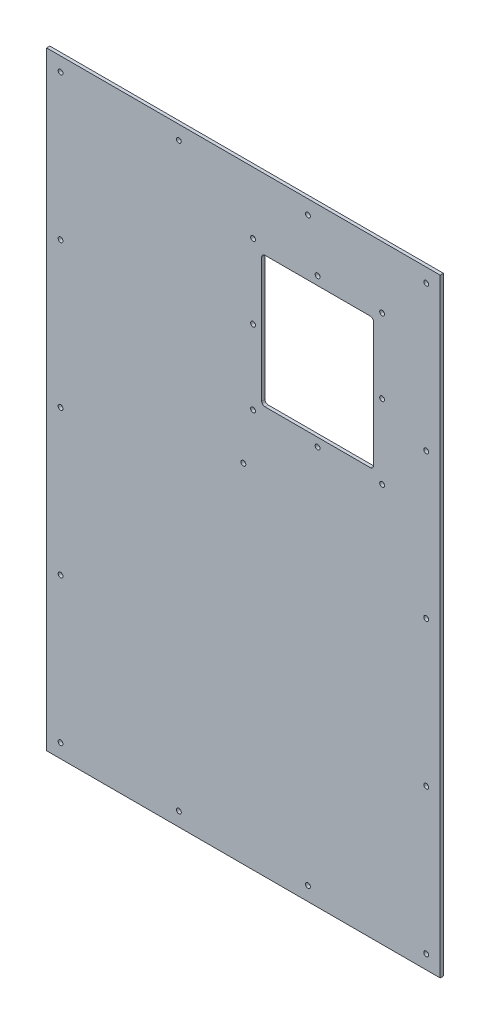
SolidWorks part; units mm, degrees
ref_plane "Спереди" through (0, 0, 0) normal (0, 0, 1) x (1, 0, 0)
ref_plane "Сверху" through (0, 0, 0) normal (0, 1, 0) x (1, 0, 0)
ref_plane "Справа" through (0, 0, 0) normal (1, 0, 0) x (0, 0, -1)
sketch "Эскиз1" plane through (0, 0, 0) normal (0, 0, 1) x (1, 0, 0)
  line L0 (0, 0) -> (366, 0)
  line L1 (0, 0) -> (0, 566)
  line L2 (366, 0) -> (366, 566)
  line L3 (0, 566) -> (366, 566)
  dimension "D1" = 566
  dimension "D2" = 366
extrude "Бобышка-Вытянуть1" add sketch "Эскиз1" along normal blind 3
sketch "Эскиз2" plane through (0, 0, 3) normal (0, 0, 1) x (1, 0, 0)
  line L0 (3, 563) -> (363, 563) construction
  line L1 (3, 563) -> (3, 3) construction
  line L2 (363, 563) -> (363, 3) construction
  line L3 (3, 3) -> (363, 3) construction
  line L4 (0, 566) -> (0, 0) construction
  line L5 (0, 0) -> (366, 0) construction
  dimension "D1" = 560
  dimension "D2" = 360
  dimension "D3" = 3
  dimension "D4" = 3
sketch "Эскиз5" plane through (0, 0, 0) normal (0, 0, -1) x (-1, 0, 0)
  line L0 (-353, 553) -> (-13, 553) construction
  line L1 (-353, 553) -> (-353, 13) construction
  line L2 (-13, 553) -> (-13, 13) construction
  line L3 (-353, 13) -> (-13, 13) construction
  line L4 (-366, 566) -> (0, 566) construction
  line L5 (-366, 0) -> (-366, 566) construction
  line L6 (0, 566) -> (0, 0) construction
  line L7 (0, 0) -> (-366, 0) construction
  line L8 (-366, 23) -> (-343, 23) construction
  line L9 (-366, 23) -> (-366, 0) construction
  line L10 (-343, 23) -> (-343, 0) construction
  line L11 (-366, 0) -> (-343, 0) construction
  line L12 (0, 0) -> (0, 23) construction
  line L13 (0, 0) -> (-23, 0) construction
  line L14 (0, 23) -> (-23, 23) construction
  line L15 (-23, 0) -> (-23, 23) construction
  line L16 (-366, 566) -> (-343, 566) construction
  line L17 (-366, 566) -> (-366, 543) construction
  line L18 (-343, 566) -> (-343, 543) construction
  line L19 (-366, 543) -> (-343, 543) construction
  line L20 (0, 566) -> (0, 543) construction
  line L21 (0, 566) -> (-23, 566) construction
  line L22 (0, 543) -> (-23, 543) construction
  line L23 (-23, 566) -> (-23, 543) construction
  line L24 (-13, 283) -> (-353, 283) construction
  line L25 (-183, 553) -> (-183, 13) construction
  circle A0 centre (-353, 553) radius 2.25
  circle A1 centre (-13, 553) radius 2.25
  circle A3 centre (-243, 553) radius 2.25
  circle A4 centre (-123, 553) radius 2.25
  circle A5 centre (-353, 418) radius 2.25
  circle A6 centre (-353, 283) radius 2.25
  circle A7 centre (-353, 148) radius 2.25
  circle A8 centre (-353, 13) radius 2.25
  circle A11 centre (-13, 418) radius 2.25
  circle A12 centre (-13, 283) radius 2.25
  circle A13 centre (-13, 148) radius 2.25
  circle A14 centre (-13, 13) radius 2.25
  circle A18 centre (-123, 13) radius 2.25
  circle A19 centre (-243, 13) radius 2.25
  dimension "D13" = 4.5
  dimension "D14" = 4.5
  dimension "D15" = 110
  dimension "D17" = 4.5
  dimension "D18" = 4.5
  dimension "D19" = 110
  dimension "D22" = 135
  dimension "D23" = 135
  dimension "D24" = 110
  dimension "D25" = 5
  dimension "D26" = 135
  dimension "D27" = 110
  dimension "D29" = 4.5
  dimension "D31" = 4.5
  dimension "D1" = 13
  dimension "D2" = 13
  dimension "D3" = 13
  dimension "D4" = 13
  dimension "D5" = 23
  dimension "D6" = 23
  dimension "D7" = 23
  dimension "D8" = 23
  dimension "D9" = 23
  dimension "D10" = 23
  dimension "D11" = 23
  dimension "D12" = 23
  dimension "D21" = 5
extrude "Вырез-Вытянуть2" cut sketch "Эскиз5" against normal through all
sketch "Эскиз6" plane through (0, 0, 3) normal (0, 0, 1) x (1, 0, 0)
  line L0 (200, 378.5) -> (200, 500.5) construction
  line L1 (200, 378.5) -> (200, 500.5)
  line L2 (200, 500.5) -> (304, 500.5) construction
  line L3 (200, 500.5) -> (304, 500.5)
  line L4 (304, 500.5) -> (304, 378.5) construction
  line L5 (304, 500.5) -> (304, 378.5)
  line L6 (304, 378.5) -> (200, 378.5) construction
  line L7 (304, 378.5) -> (200, 378.5)
extrude "Вырез-Вытянуть3" cut sketch "Эскиз6" against normal through all
sketch "Эскиз7" plane through (0, 0, 3) normal (0, 0, 1) x (1, 0, 0)
  circle A0 centre (192, 370.5) radius 2.25 construction
  circle A1 centre (192, 370.5) radius 2.25
  circle A2 centre (192, 439.5) radius 2.25 construction
  circle A3 centre (192, 439.5) radius 2.25
  circle A4 centre (192, 508.5) radius 2.25 construction
  circle A5 centre (192, 508.5) radius 2.25
  circle A6 centre (252, 370.5) radius 2.25 construction
  circle A7 centre (252, 370.5) radius 2.25
  circle A8 centre (312, 370.5) radius 2.25 construction
  circle A9 centre (312, 370.5) radius 2.25
  circle A10 centre (252, 508.5) radius 2.25 construction
  circle A11 centre (252, 508.5) radius 2.25
  circle A12 centre (312, 508.5) radius 2.25 construction
  circle A13 centre (312, 508.5) radius 2.25
  circle A14 centre (312, 439.5) radius 2.25 construction
  circle A15 centre (312, 439.5) radius 2.25
  circle A16 centre (312, 370.5) radius 2.25
extrude "Вырез-Вытянуть4" cut sketch "Эскиз7" against normal through all contours A3 | A11 | A13 | A15 | A9 | A7 | A1 | A5 region at (192, 370.5, 3) region at (192, 439.5, 3) region at (252, 370.5, 3) region at (312, 370.5, 3) region at (252, 508.5, 3) region at (312, 508.5, 3) region at (312, 439.5, 3)
sketch "Sketch1" plane through (0, 0, 3) normal (0, 0, 1) x (1, 0, 0)
  line L0 (343, 333) -> (23, 333) construction
  line L1 (343, 333) -> (23, 333) construction
  line L2 (343, 313) -> (23, 313) construction
  line L3 (343, 313) -> (23, 313) construction
  line L4 (183, 333) -> (183, 313) construction
  circle A0 centre (183, 323) radius 2.25
  dimension "D1" = 4.5
  dimension "D2" = 10
extrude "Cut-Extrude1" cut sketch "Sketch1" against normal through all
fillet "Fillet2" radius 3 4 edges at (200, 378.5, 1.5) (304, 378.5, 1.5) (304, 500.5, 1.5) (200, 500.5, 1.5)
